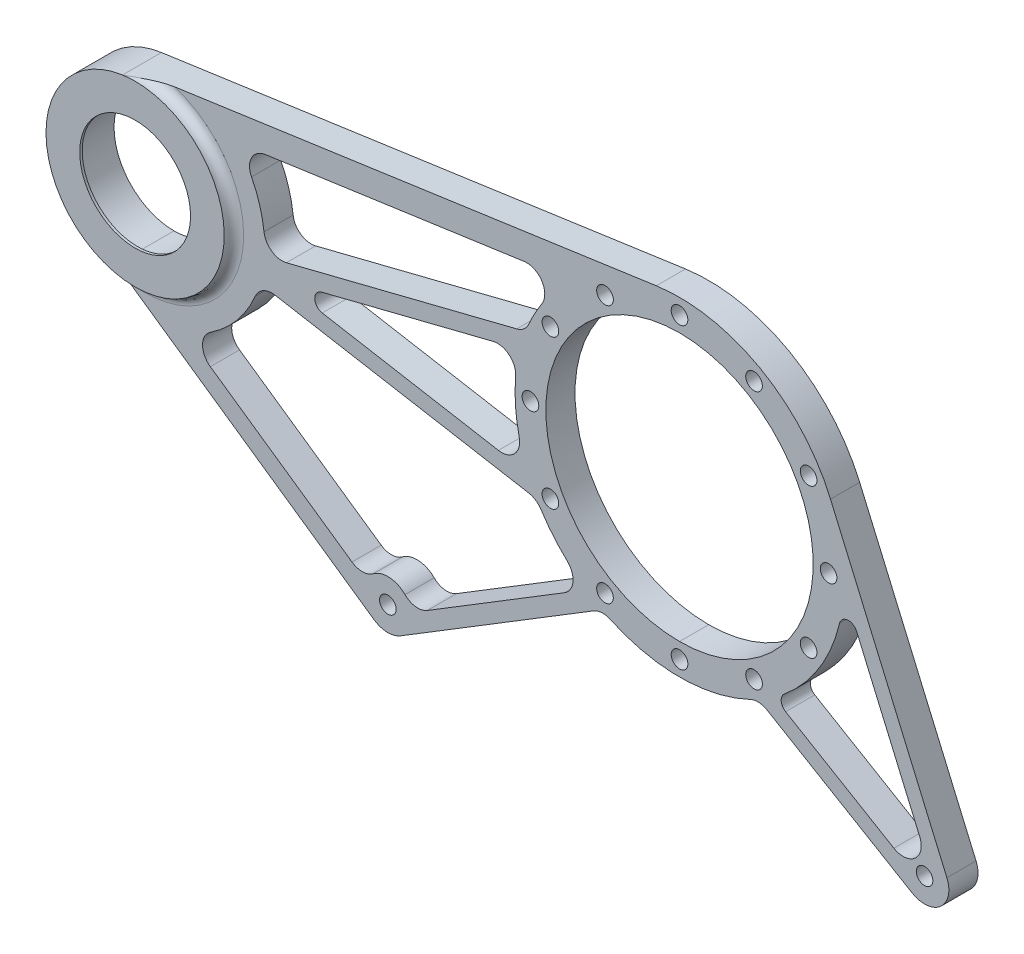
SolidWorks part; units mm, degrees
material "6061-T6 (SS)"
ref_plane "Front Plane" through (0, 0, 0) normal (0, 0, 1) x (1, 0, 0)
ref_plane "Top Plane" through (0, 0, 0) normal (0, 1, 0) x (1, 0, 0)
ref_plane "Right Plane" through (0, 0, 0) normal (1, 0, 0) x (0, 0, -1)
sketch "Sketch1" plane through (0, 0, 0) normal (0, 0, 1) x (1, 0, 0)
  line L0 (-328.7713, 136.1765) -> (-123.3819, 165.4094)
  line L1 (-343.7594, 72.9056) -> (-234.0298, -3.2296)
  line L2 (-223.6277, -3.528) -> (-148.0091, 42.7538)
  line L3 (-114.3, 88.9) -> (-114.3, 101.6) construction
  line L4 (-55.1193, 127.1299) -> (-9.5189, 21.4239)
  line L5 (-23.1153, 9.4535) -> (-80.0139, 43.1208)
  circle A0 centre (-114.3, 88.9) radius 82.9716 construction
  circle A1 centre (-228.6, -20.8038) radius 12.7 construction
  circle A2 centre (0, 0) radius 12.7 construction
  circle A3 centre (-323.85, 101.6) radius 114 construction
  circle A4 centre (-323.85, 101.6) radius 23.5
  circle A5 centre (-114.3, 101.6) radius 52.3875
  arc A6 (-141.4233, 43.1325) -> (-86.5756, 43.4151) centre (-114.3, 101.6) ccw
  circle A7 centre (-323.85, 101.6) radius 34.925
  arc A8 (-223.6277, -3.528) -> (-234.0298, -3.2296) centre (-228.6, 4.5962) cw
  arc A9 (-9.5189, 21.4239) -> (-23.1153, 9.4535) centre (-18.2648, 17.651) cw
  circle A10 centre (-228.6, 4.5962) radius 3.2512
  circle A11 centre (-18.2648, 17.651) radius 3.2512
  arc A12 (-141.4233, 43.1325) -> (-148.0091, 42.7538) centre (-144.3627, 36.7961) ccw
  arc A13 (-80.0139, 43.1208) -> (-86.5756, 43.4151) centre (-83.571, 37.1094) ccw
  arc A14 (-141.4233, 43.1325) -> (-86.5756, 43.4151) centre (-114.3, 101.6) ccw construction
  arc A15 (-123.3819, 165.4094) -> (-55.1193, 127.1299) centre (-114.3, 101.6) cw
  arc A16 (-141.4233, 43.1325) -> (-86.5756, 43.4151) centre (-114.3, 101.6) ccw
  arc A17 (-55.1193, 127.1299) -> (-123.3819, 165.4094) centre (-114.3, 101.6) ccw construction
  dimension "D1" = 88.9
  dimension "D2" = 12.7
  dimension "D3" = 25.4
  dimension "D4" = 25.4
  dimension "D8" = 165.9433
  dimension "D9" = 228
  dimension "D10" = 47
  dimension "D12" = 104.775
  dimension "D15" = 69.85
  dimension "D16" = 9.525
  dimension "D18" = 9.525
  dimension "D20" = 6.5024
  dimension "D21" = 6.5024
  dimension "D23" = 6.985
  dimension "D24" = 6.985
  dimension "D25" = 128.905
  dimension "D5" = 228.6
  dimension "D6" = 20.8038
  dimension "D7" = 114.3
  dimension "D11" = 12.7
  dimension "D13" = 209.55
  dimension "D17" = 25.4
  dimension "D19" = 25.4
  dimension "D22" = 17.651
extrude "Boss-Extrude1" add sketch "Sketch1" along normal blind 11.43 contours A7 A4 | A8 L2 A6 L0 A7 L1 A10 | A6 A5 | A9 L4 A6 L5 A11 region at (-188.8604, 80.9757, 0) region at (-301.6077, 127.2322, 0)
ref_point "Point2"
ref_point "Point4"
ref_plane "Plane2" through (-114.3, 0, 0) normal (1, 0, 0) x (0, 0, -1)
ref_plane "Plane3" through (-323.85, 0, 0) normal (1, 0, 0) x (0, 0, -1)
sketch "Sketch5" plane through (0, 0, 11.43) normal (0, 0, 1) x (1, 0, 0)
  circle A0 centre (-323.85, 101.6) radius 23.5
  circle A1 centre (-323.85, 101.6) radius 34.925
extrude "Boss-Extrude3" add sketch "Sketch5" along normal blind 3.81
fillet "Fillet2" radius 3.81 1 edges at (-289.8655, 93.5495, 11.43)
sketch "Sketch6" plane through (0, 0, 15.24) normal (0, 0, 1) x (1, 0, 0)
  circle A0 centre (-323.85, 101.6) radius 23.5
  circle A1 centre (-323.85, 101.6) radius 21.722
  dimension "D1" = 47
  dimension "D2" = 1.778
extrude "Boss-Extrude4" add sketch "Sketch6" against normal blind 0.9677
split line "Split Line3"
split line "Split Line4"
sketch "Sketch8" plane through (0, 0, 11.43) normal (0, 0, 1) x (1, 0, 0)
  line L0 (-114.3, 101.6) -> (-114.3, 160.02) construction
  circle A20 centre (-114.3, 101.6) radius 58.42 construction
  circle A21 centre (-114.3, 160.02) radius 3.2639
  circle A22 centre (-85.09, 152.1932) radius 3.2639
  circle A23 centre (-63.7068, 130.81) radius 3.2639
  circle A24 centre (-55.88, 101.6) radius 3.2639
  circle A25 centre (-63.7068, 72.39) radius 3.2639
  circle A26 centre (-85.09, 51.0068) radius 3.2639
  circle A27 centre (-114.3, 43.18) radius 3.2639
  circle A28 centre (-143.51, 51.0068) radius 3.2639
  circle A29 centre (-164.8932, 72.39) radius 3.2639
  circle A30 centre (-172.72, 101.6) radius 3.2639
  circle A31 centre (-164.8932, 130.81) radius 3.2639
  circle A32 centre (-143.51, 152.1932) radius 3.2639
  point P22 (-114.3, 101.6)
  point P31 (-112.8188, 101.2031)
  point P32 (-114.3, 101.6)
  dimension "D1" = 116.84
  dimension "D2" = 6.5278
  dimension "D3" = 12
extrude "Cut-Extrude3" cut sketch "Sketch8" against normal through all both and the other way through all
sketch "Sketch9" plane through (0, 0, 11.43) normal (0, 0, 1) x (1, 0, 0)
  line L0 (-72.7119, 46.1785) -> (-30.2936, 21.0793)
  line L1 (-44.8609, 87.3188) -> (-20.1416, 30.0172)
  line L2 (-55.1193, 127.1299) -> (-9.5189, 21.4239) construction
  line L3 (-23.1153, 9.4535) -> (-80.0139, 43.1208) construction
  line L4 (-276.7089, 133.3241) -> (-175.2231, 147.7685)
  line L5 (-312.1859, 138.5371) -> (-123.3819, 165.4094) construction
  line L6 (-298.1775, 50.5534) -> (-242.6682, 12.0387)
  line L7 (-159.4172, 43.2165) -> (-213.1554, 10.3264)
  line L8 (-268.3544, 100.7495) -> (-178.1187, 123.4164)
  line L9 (-329.9956, 63.3556) -> (-234.0298, -3.2296) construction
  line L10 (-272.8019, 87.5079) -> (-173.3699, 70.0625)
  line L11 (-223.6277, -3.528) -> (-148.0091, 42.7538) construction
  line L12 (-187.3406, 114.5526) -> (-254.5737, 97.6639)
  line L13 (-254.3219, 90.7125) -> (-185.2831, 78.5997)
  arc A0 (-73.1703, 51.9767) -> (-51.5862, 86.7306) centre (-114.3, 101.6) ccw
  arc A1 (-30.2936, 21.0793) -> (-20.1416, 30.0172) centre (-26.6719, 27.2001) ccw
  arc A2 (-44.8609, 87.3188) -> (-51.5862, 86.7306) centre (-48.1261, 85.9103) ccw
  arc A3 (-72.7119, 46.1785) -> (-73.1703, 51.9767) centre (-70.901, 49.2389) cw
  arc A4 (-276.9566, 98.5887) -> (-278.7101, 88.5445) centre (-323.85, 101.6) ccw construction
  arc A5 (-176.8384, 117.1907) -> (-173.6921, 76.5661) centre (-114.3, 101.6) ccw construction
  arc A6 (-221.8833, 11.3498) -> (-234.3332, 12.2025) centre (-228.6, 4.5962) ccw
  arc A7 (-213.1554, 10.3264) -> (-221.8833, 11.3498) centre (-216.8681, 16.3924) cw
  arc A8 (-242.6682, 12.0387) -> (-234.3332, 12.2025) centre (-238.6139, 17.8819) ccw
  arc A9 (-282.0355, 123.0384) -> (-277.1545, 106.8523) centre (-323.85, 101.6) cw
  arc A10 (-168.266, 136.839) -> (-173.3369, 127.4605) centre (-114.3, 101.6) ccw
  arc A11 (-159.4172, 43.2165) -> (-158.2772, 54.4818) centre (-163.1299, 49.2825) ccw
  arc A12 (-298.1775, 50.5534) -> (-298.031, 62.3389) centre (-294.1232, 56.3966) cw
  arc A13 (-175.2231, 147.7685) -> (-168.266, 136.839) centre (-174.2209, 140.7275) cw
  arc A14 (-276.7089, 133.3241) -> (-282.0355, 123.0384) centre (-275.7068, 126.2831) ccw
  arc A15 (-280.5799, 83.2762) -> (-298.031, 62.3389) centre (-323.85, 101.6) cw
  arc A16 (-178.5214, 107.0532) -> (-177.122, 87.1943) centre (-114.3, 101.6) ccw
  arc A17 (-170.1932, 69.5052) -> (-174.625, 124.294) centre (-114.3, 101.6) ccw construction
  arc A18 (-168.6064, 66.8878) -> (-158.2772, 54.4818) centre (-114.3, 101.6) ccw
  arc A19 (-178.1187, 123.4164) -> (-173.3369, 127.4605) centre (-179.8514, 130.3141) ccw
  arc A20 (-173.3699, 70.0625) -> (-168.6064, 66.8878) centre (-174.5989, 63.0575) cw
  arc A21 (-272.8019, 87.5079) -> (-280.5799, 83.2762) centre (-274.031, 80.5029) ccw
  arc A22 (-268.3544, 100.7495) -> (-277.1545, 106.8523) centre (-270.087, 107.6472) cw
  arc A23 (-187.3406, 114.5526) -> (-178.5214, 107.0532) centre (-185.6079, 107.6549) cw
  arc A24 (-185.2831, 78.5997) -> (-177.122, 87.1943) centre (-184.0541, 85.6047) ccw
  arc A25 (-254.5737, 97.6639) -> (-254.3219, 90.7125) centre (-253.7074, 94.215) ccw
  point P41 (-150.8092, 48.485)
  point P44 (-307.9954, 57.3655)
  point P47 (-156.3377, 150.4565)
  point P50 (-287.8037, 131.745)
  point P55 (0, 0)
  point P57 (0, 0)
  point P58 (0, 0)
  point P59 (0, 0)
  point P60 (0, 0)
  dimension "D2" = 128.905
  dimension "D4" = 14.224
  dimension "D5" = 3.556
  dimension "D6" = 93.98
  dimension "D7" = 128.905
  dimension "D9" = 19.05
  dimension "D12" = 7.112
  dimension "D13" = 7.112
  dimension "D16" = 7.112
  dimension "D17" = 7.112
  dimension "D18" = 3.556
  dimension "D1" = 6.35
  dimension "D3" = 6.35
  dimension "D8" = 10.16
  dimension "D10" = 7.62
  dimension "D11" = 6.35
  dimension "D14" = 6.35
  dimension "D15" = 6.35
extrude "Cut-Extrude5" cut sketch "Sketch9" against normal through all contours L4 A14 A9 L8 A10 A13 | A12 L6 A8 A6 A7 L7 A11 A10 L10 A9 | A3 L0 A1 L1 A2 A0 | A10 L12 L13 region at (-45.3246, 50.9255, 11.43) region at (-228.2185, 125.9037, 11.43) region at (-229.9519, 50.2167, 11.43) region at (-208.2584, 95.7863, 11.43)
sketch "Sketch7" plane through (0, 0, 0) normal (0, 0, 1) x (1, 0, 0)
  line L0 (-276.8856, 133.299) -> (-174.9449, 147.8081)
  line L1 (-299.5603, 140.3341) -> (-125.0224, 165.1759)
  line L2 (-312.1859, 138.5371) -> (-123.3819, 165.4094) construction
  line L3 (-329.9956, 63.3556) -> (-234.0298, -3.2296) construction
  line L4 (-329.9956, 63.3556) -> (-319.5178, 56.0857) construction
  line L5 (-295.4693, 48.6743) -> (-242.5925, 11.9861)
  line L6 (-213.2408, 10.2742) -> (-159.2746, 43.3038)
  line L7 (-223.6277, -3.528) -> (-148.0091, 42.7538) construction
  line L8 (-223.6277, -3.528) -> (-148.0091, 42.7538) construction
  line L9 (-292.4716, 61.3285) -> (-179.5871, 77.3953)
  line L10 (-272.8543, 74.383) -> (-184.3367, 86.9817)
  line L11 (-29.9577, 20.8806) -> (-72.7896, 46.2245)
  line L12 (-19.9871, 29.6588) -> (-44.937, 87.4951)
  line L13 (-23.1153, 9.4535) -> (-80.0139, 43.1208) construction
  line L14 (-55.1193, 127.1299) -> (-9.5189, 21.4239) construction
  line L15 (-23.1153, 9.4535) -> (-80.0139, 43.1208) construction
  line L16 (-55.1193, 127.1299) -> (-9.5189, 21.4239) construction
  line L17 (-312.1859, 138.5371) -> (-123.3819, 165.4094) construction
  line L18 (-278.2115, 104.2679) -> (-178.0675, 117.6829) construction
  line L19 (-272.0734, 112.7782) -> (-177.8671, 125.3978)
  line L20 (-269.4316, 101.6) -> (-177.5668, 113.9059) construction
  line L22 (-186.5425, 112.7036) -> (-271.2809, 101.3523)
  circle A0 centre (-114.3, 101.6) radius 62.0284 construction
  circle A1 centre (-323.85, 101.6) radius 39.37 construction
  arc A4 (-292.4716, 61.3285) -> (-295.4693, 48.6743) centre (-291.4874, 54.4132) ccw
  arc A5 (-172.3155, 73.5228) -> (-158.1669, 54.379) centre (-114.3, 101.6) ccw
  arc A6 (-158.1669, 54.379) -> (-159.2746, 43.3038) centre (-162.9209, 49.2615) cw
  arc A7 (-179.5871, 77.3953) -> (-172.3155, 73.5228) centre (-178.6029, 70.48) cw
  arc A8 (-282.1065, 123.1764) -> (-279.5813, 117.3588) centre (-323.85, 101.6) cw
  arc A9 (-168.1271, 137.0509) -> (-172.4884, 129.3171) centre (-114.3, 101.6) ccw
  arc A10 (-178.3767, 94.6501) -> (-184.3367, 86.9817) centre (-185.321, 93.897) cw
  arc A11 (-282.1065, 123.1764) -> (-276.8856, 133.299) centre (-275.9014, 126.3837) cw
  arc A12 (-280.3106, 83.9256) -> (-272.8543, 74.383) centre (-273.8386, 81.2983) ccw
  arc A13 (-174.9449, 147.8081) -> (-168.1271, 137.0509) centre (-173.9606, 140.8928) cw
  arc A14 (-221.8426, 11.3091) -> (-234.3754, 12.1705) centre (-228.6, 4.5962) ccw
  arc A15 (-223.6277, -3.528) -> (-223.0453, -3.1415) centre (-228.6, 4.5962) ccw
  arc A16 (-234.3754, 12.1705) -> (-242.5925, 11.9861) centre (-238.6106, 17.725) cw
  arc A17 (-213.2408, 10.2742) -> (-221.8426, 11.3091) centre (-216.8872, 16.2319) cw
  arc A19 (-19.9871, 29.6588) -> (-29.9577, 20.8806) centre (-26.4007, 26.892) cw
  arc A20 (-73.2362, 51.9221) -> (-51.5444, 86.9079) centre (-114.3, 101.6) ccw
  arc A21 (-44.937, 87.4951) -> (-51.5444, 86.9079) centre (-48.1438, 86.1117) ccw
  arc A22 (-72.7896, 46.2245) -> (-73.2362, 51.9221) centre (-71.0111, 49.2302) cw
  arc A23 (-177.5668, 113.9059) -> (-173.9892, 125.9173) centre (-114.3, 101.6) ccw construction
  arc A24 (-277.2765, 95.3571) -> (-280.3106, 83.9256) centre (-323.85, 101.6) cw
  arc A25 (-178.642, 105.3717) -> (-178.3767, 94.6501) centre (-114.3, 101.6) ccw
  arc A26 (-172.4884, 129.3171) -> (-177.8671, 125.3978) centre (-178.7945, 132.3209) cw
  arc A27 (-178.642, 105.3717) -> (-186.5425, 112.7036) centre (-185.6151, 105.7804) ccw
  arc A28 (-272.0734, 112.7782) -> (-279.5813, 117.3588) centre (-273.0008, 119.7014) cw
  arc A29 (-271.2809, 101.3523) -> (-277.2765, 95.3571) centre (-270.3535, 94.4291) ccw
  point P31 (-310.0925, 58.8205)
  point P33 (-172.4396, 79.9826)
  point P41 (-287.8037, 131.745)
  point P45 (-154.09, 149.1844)
  point P64 (-78.8001, 50.7347)
  dimension "D3" = 7.62
  dimension "D5" = 46.99
  dimension "D6" = 124.0568
  dimension "D7" = 6.985
  dimension "D8" = 6.985
  dimension "D10" = 6.985
  dimension "D11" = 9.525
  dimension "D12" = 6.985
  dimension "D13" = 6.985
  dimension "D16" = 3.4925
  dimension "D17" = 128.905
  dimension "D22" = 6.985
  dimension "D2" = 10.16
  dimension "D4" = 6.35
  dimension "D9" = 10.16
  dimension "D14" = 6.35
  dimension "D15" = 6.35
  dimension "D18" = 3.81
  dimension "D19" = 11.43
  dimension "D20" = 0.471
  dimension "D21" = 101.0385
